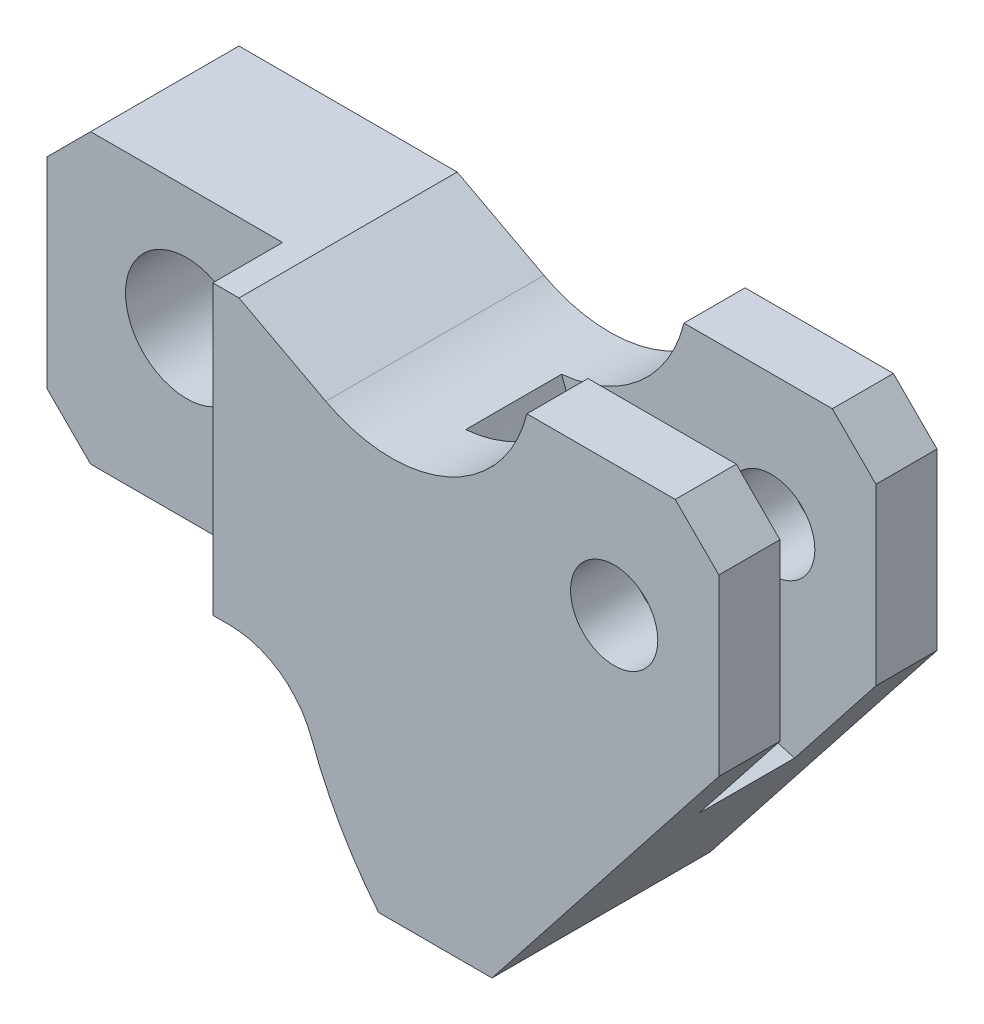
SolidWorks part; units mm, degrees
ref_plane "Front Plane" through (0, 0, 0) normal (0, 0, 1) x (1, 0, 0)
ref_plane "Top Plane" through (0, 0, 0) normal (0, 1, 0) x (1, 0, 0)
ref_plane "Right Plane" through (0, 0, 0) normal (1, 0, 0) x (0, 0, -1)
sketch "Sketch1" plane through (0, 0, 0) normal (0, 0, 1) x (1, 0, 0)
  line L8 (15.5324, -3.84) -> (37.5324, -3.84)
  line L9 (37.5324, -3.84) -> (37.5324, -28.84)
  line L10 (37.5324, -28.84) -> (11.5324, -61.84)
  line L11 (11.5324, -61.84) -> (-1.4676, -61.84)
  line L12 (-47.4676, -8.84) -> (-17.4552, -8.84)
  line L13 (-47.4676, -8.84) -> (-47.4676, -41.84)
  line L14 (-47.4676, -41.84) -> (-18.5358, -41.84)
  line L15 (-17.4552, -8.84) -> (-7.5115, -14.1272)
  line L16 (-20.4676, -8.84) -> (-20.4676, -41.84)
  arc A7 (-7.5115, -14.1272) -> (15.5324, -3.84) centre (0, 0) ccw
  circle A8 centre (25.5324, -18.84) radius 5
  circle A9 centre (-31.4676, -22.84) radius 7
  arc A10 (-18.5358, -41.84) -> (-9.1531, -48.3809) centre (-18.5358, -51.84) cw
  arc A11 (-9.1531, -48.3809) -> (-1.4676, -61.84) centre (34.9455, -32.1233) ccw
  arc A12 (1.5066, -15.9289) -> (28.2057, -40.6777) centre (37.5324, -3.84) ccw
  dimension "D8" = 12
  dimension "D9" = 15
  dimension "D10" = 3.84
  dimension "D11" = 33
  dimension "D15" = 10
  dimension "D18" = 85
  dimension "D1" = 47
  dimension "D2" = 10
  dimension "D6" = 32
  dimension "D14" = 14
  dimension "D3" = 13
  dimension "D4" = 26
  dimension "D5" = 25
  dimension "D7" = 22
  dimension "D12" = 14
  dimension "D13" = 16
  dimension "D16" = 58
  dimension "D17" = 20
  dimension "D19" = 28
  dimension "D20" = 27
extrude "Boss-Extrude1" add sketch "Sketch1" along normal blind 17 from offset 12.5 contours L16 L12 L13 L14 A9 region at (-20.894, -25.34, 0) offset against normal yes
extrude "Boss-Extrude3" add sketch "Sketch1<4>" along normal mid plane 25 contours A12 A7 L15 L12 L16 L14 A10 A11 L11 L10 region at (-0.5859, -37.2198, 0)
sketch "Sketch1<4>" plane through (0, 0, 0) normal (0, 0, 1) x (1, 0, 0) same geometry as "Sketch1"
extrude "Boss-Extrude4" add sketch "Sketch1<5>" along normal blind 7 from offset 5.5 contours A7 A12 L10 L9 L8 A8 region at (26.5324, -4.3553, 0)
sketch "Sketch1<5>" plane through (0, 0, 0) normal (0, 0, 1) x (1, 0, 0) same geometry as "Sketch1"
mirror "Mirror1" about plane through (0, 0, 0) normal (0, 0, 1) of "Boss-Extrude4"
chamfer "Chamfer1" distance 5 angle 45 4 edges at (37.5324, -3.84, 9) (37.5324, -3.84, -9) (-47.4676, -41.84, -4) (-47.4676, -8.84, -4)
